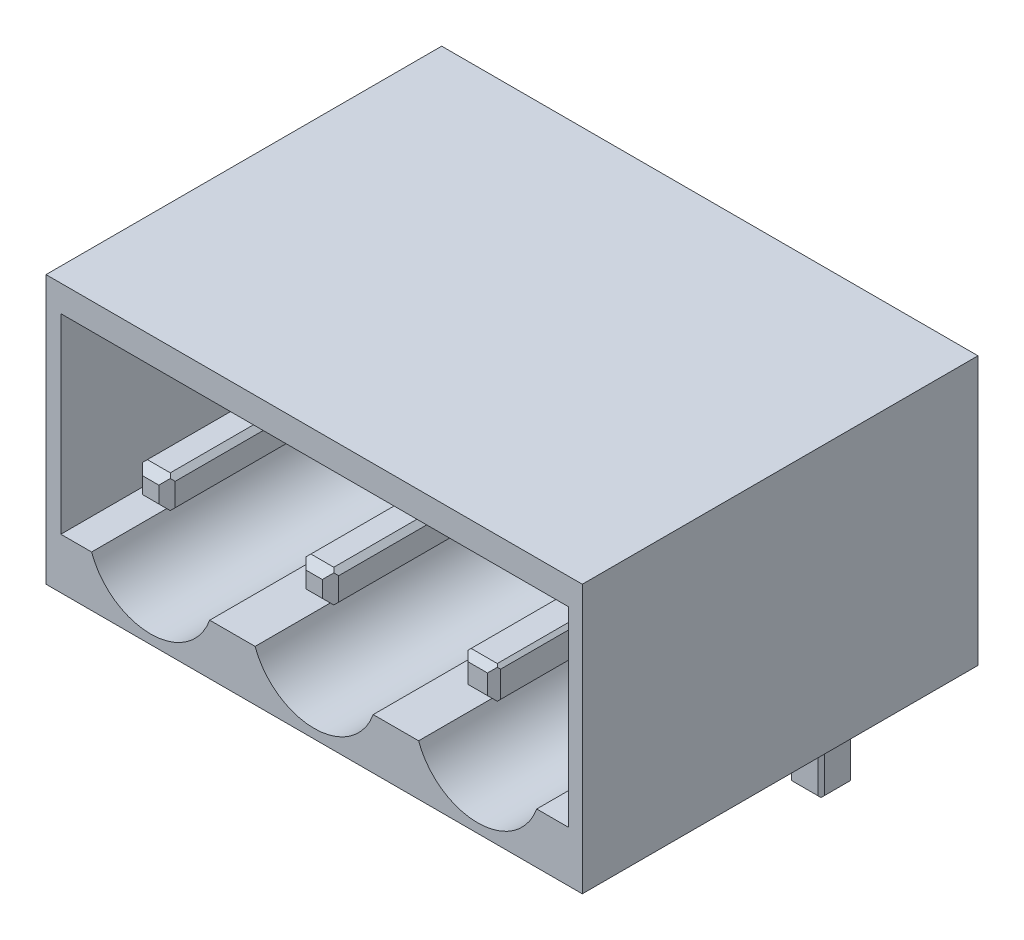
SolidWorks part; units mm, degrees
ref_plane "Спереди" through (0, 0, 0) normal (0, 0, 1) x (1, 0, 0)
ref_plane "Сверху" through (0, 0, 0) normal (0, 1, 0) x (1, 0, 0)
ref_plane "Справа" through (0, 0, 0) normal (1, 0, 0) x (0, 0, -1)
sketch "Эскиз1" plane through (0, 0, 0) normal (0, 0, 1) x (1, 0, 0)
  line L1 (-8.2, 4.1) -> (8.2, 4.1)
  line L2 (-8.2, 4.1) -> (-8.2, -4.1)
  line L3 (-8.2, -4.1) -> (8.2, -4.1)
  line L4 (8.2, 4.1) -> (8.2, -4.1)
  line L5 (-8.2, 4.1) -> (8.2, -4.1) construction
  line L6 (-8.2, -4.1) -> (8.2, 4.1) construction
  point P0 (0, 0)
  dimension "D1" = 8.2
  dimension "D2" = 16.4
extrude "Бобышка-Вытянуть1" add sketch "Эскиз1" along normal blind 12.1
sketch "Эскиз4" plane through (0, 0, 12.1) normal (0, 0, 1) x (1, 0, 0)
  circle A0 centre (-5, 0) radius 1.25
  circle A1 centre (0, 0) radius 1.25
  circle A2 centre (5, 0) radius 1.25
  dimension "D1" = 2.5
  dimension "D2" = 5
  dimension "D3" = 2
  dimension "D4" = 2
extrude "Вырез-Вытянуть3" cut sketch "Эскиз4" against normal blind 8
sketch "Эскиз5" plane through (0, 0, 12.1) normal (0, 0, 1) x (1, 0, 0)
  line L0 (-7.7456, 0) -> (-7.7456, 3.2929)
  line L1 (-7.7456, 3.2929) -> (2.7785, 3.2929)
  line L4 (-7.7456, -2.549) -> (-7.7456, 0)
  line L5 (1.8058, -2.549) -> (3.1942, -2.549)
  line L6 (-6.8058, -2.549) -> (-7.7456, -2.549)
  line L7 (-3.1942, -2.549) -> (-1.8058, -2.549)
  line L9 (6.8058, -2.549) -> (7.7785, -2.549)
  line L10 (7.7785, 3.2929) -> (7.7785, -2.549)
  line L11 (2.7785, 3.2929) -> (7.7785, 3.2929)
  line L13 (1.8058, -2.549) -> (3.1942, -2.549) [skipped]
  arc A1 (3.1942, -2.549) -> (6.8058, -2.549) centre (5, -1.9) ccw
  arc A5 (-6.8058, -2.549) -> (-3.1942, -2.549) centre (-5, -1.9) ccw
  arc A6 (-1.8058, -2.549) -> (1.8058, -2.549) centre (0, -1.9) ccw
  dimension "D1" = 3.2
  dimension "D2" = 2.2
  dimension "D3" = 2
  dimension "D4" = 2
extrude "Вырез-Вытянуть4" cut sketch "Эскиз5" against normal blind 7.8
sketch "Эскиз7" plane through (0, 0, 4.1) normal (0, 0, 1) x (1, 0, 0)
  line L0 (-0.5, 0.5) -> (0.5, 0.5)
  line L1 (-5.5, 0.5) -> (-4.5, 0.5)
  line L2 (-5.5, 0.5) -> (-5.5, -0.5)
  line L3 (-5.5, -0.5) -> (-4.5, -0.5)
  line L4 (-4.5, 0.5) -> (-4.5, -0.5)
  line L5 (-5.5, 0.5) -> (-4.5, -0.5) construction
  line L6 (-5.5, -0.5) -> (-4.5, 0.5) construction
  line L7 (-0.5, 0.5) -> (-0.5, -0.5)
  line L8 (-0.5, -0.5) -> (0.5, -0.5)
  line L9 (0.5, 0.5) -> (0.5, -0.5)
  line L10 (-0.5, 0.5) -> (0.5, -0.5) construction
  line L11 (-0.5, -0.5) -> (0.5, 0.5) construction
  line L12 (4.5, 0.5) -> (5.5, 0.5)
  line L13 (4.5, 0.5) -> (4.5, -0.5)
  line L14 (4.5, -0.5) -> (5.5, -0.5)
  line L15 (5.5, 0.5) -> (5.5, -0.5)
  line L16 (4.5, 0.5) -> (5.5, -0.5) construction
  line L17 (4.5, -0.5) -> (5.5, 0.5) construction
  point P0 (-5, 0)
  point P7 (0, 0)
  point P12 (5, 0)
  dimension "D1" = 1
  dimension "D2" = 1
  dimension "D3" = 2
  dimension "D4" = 2
extrude "Бобышка-Вытянуть2" add sketch "Эскиз7" along normal blind 8
chamfer "Фаска1" distance 0.15 angle 45 8 edges at (-0.5, -0.5, 8.1) (-0.5, 0.5, 8.1) (0.5, 0.5, 8.1) (0.5, -0.5, 8.1) (-4.5, -0.5, 8.1) (-4.5, 0.5, 8.1) (-5.5, -0.5, 8.1) (-5.5, 0.5, 8.1)
chamfer "Фаска2" distance 0.25 angle 45 8 edges at (-0.5, 0, 12.1) (0, 0.5, 12.1) (0.5, 0, 12.1) (0, -0.5, 12.1) (-4.5, 0, 12.1) (-5, -0.5, 12.1) (-5.5, 0, 12.1) (-5, 0.5, 12.1)
sketch "Эскиз8" plane through (0, -4.1, 0) normal (0, -1, 0) x (-1, 0, 0)
  line L0 (0.5, -2.1) -> (-0.5, -2.1)
  line L1 (5.5, -2.1) -> (4.5, -2.1)
  line L2 (5.5, -2.1) -> (5.5, -1.1)
  line L3 (5.5, -1.1) -> (4.5, -1.1)
  line L4 (4.5, -2.1) -> (4.5, -1.1)
  line L5 (5.5, -2.1) -> (4.5, -1.1) construction
  line L6 (5.5, -1.1) -> (4.5, -2.1) construction
  line L7 (0.5, -2.1) -> (0.5, -1.1)
  line L8 (0.5, -1.1) -> (-0.5, -1.1)
  line L9 (-0.5, -2.1) -> (-0.5, -1.1)
  line L10 (0.5, -2.1) -> (-0.5, -1.1) construction
  line L11 (0.5, -1.1) -> (-0.5, -2.1) construction
  line L12 (-4.5, -2.1) -> (-5.5, -2.1)
  line L13 (-4.5, -2.1) -> (-4.5, -1.1)
  line L14 (-4.5, -1.1) -> (-5.5, -1.1)
  line L15 (-5.5, -2.1) -> (-5.5, -1.1)
  line L16 (-4.5, -2.1) -> (-5.5, -1.1) construction
  line L17 (-4.5, -1.1) -> (-5.5, -2.1) construction
  point P0 (5, -1.6)
  point P7 (0, -1.6)
  point P12 (-5, -1.6)
  dimension "D1" = 1
  dimension "D2" = 1
  dimension "D3" = 3.2
  dimension "D4" = 1.6
  dimension "D5" = 2
  dimension "D6" = 2
extrude "Бобышка-Вытянуть3" add sketch "Эскиз8" along normal blind 4
chamfer "Фаска3" distance 0.15 angle 45 8 edges at (-4.5, -6.1, 1.1) (0.5, -6.1, 1.1) (-5.5, -6.1, 1.1) (-4.5, -6.1, 2.1) (0.5, -6.1, 2.1) (-0.5, -6.1, 1.1) (-0.5, -6.1, 2.1) (-5.5, -6.1, 2.1)
chamfer "Фаска4" distance 0.25 angle 45 8 edges at (0.5, -8.1, 1.6) (-0.5, -8.1, 1.6) (0, -8.1, 2.1) (0, -8.1, 1.1) (-5.5, -8.1, 1.6) (-5, -8.1, 2.1) (-4.5, -8.1, 1.6) (-5, -8.1, 1.1)
chamfer "Фаска6" distance 0.1 angle 45 4 edges at (4.5, -0.5, 8.1) (5.5, -0.5, 8.1) (5.5, 0.5, 8.1) (4.5, 0.5, 8.1)
chamfer "Фаска7" distance 0.2 angle 45 4 edges at (5.5, 0, 12.1) (5, -0.5, 12.1) (4.5, 0, 12.1) (5, 0.5, 12.1)
chamfer "Фаска8" distance 0.1 angle 45 4 edges at (4.5, -6.1, 1.1) (5.5, -6.1, 1.1) (4.5, -6.1, 2.1) (5.5, -6.1, 2.1)
chamfer "Фаска9" distance 0.2 angle 45 4 edges at (5.5, -8.1, 1.6) (5, -8.1, 1.1) (4.5, -8.1, 1.6) (5, -8.1, 2.1)
